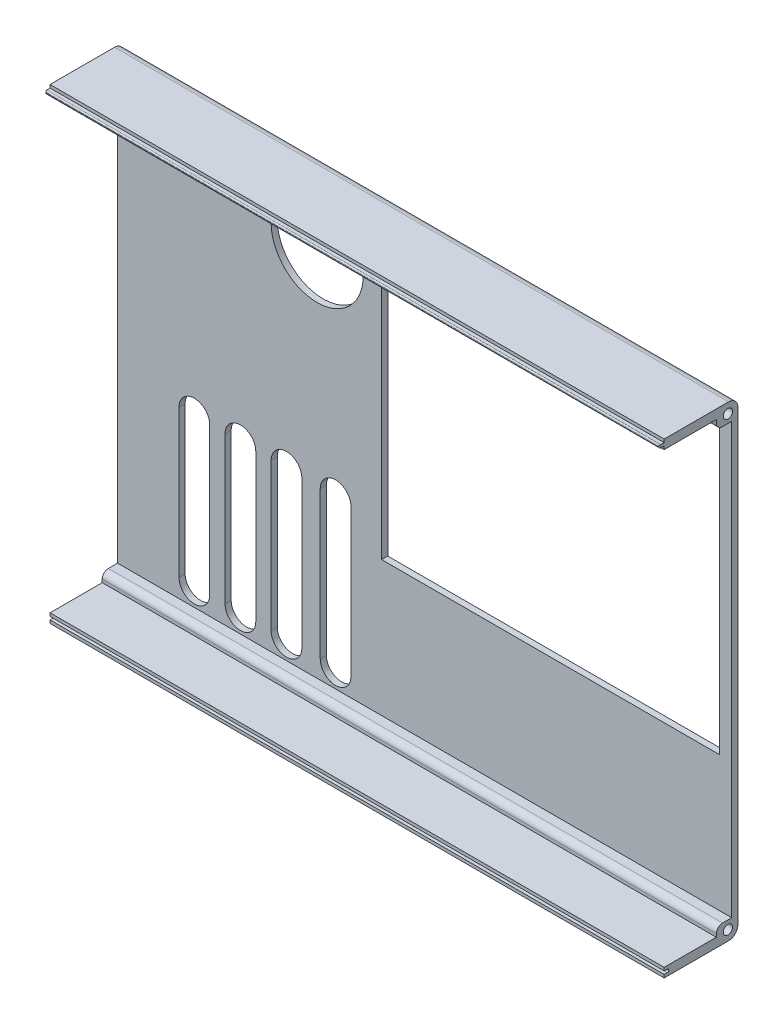
SolidWorks part; units mm, degrees
ref_plane "Front Plane" through (0, 0, 0) normal (0, 0, 1) x (1, 0, 0)
ref_plane "Top Plane" through (0, 0, 0) normal (0, 1, 0) x (1, 0, 0)
ref_plane "Right Plane" through (0, 0, 0) normal (1, 0, 0) x (0, 0, -1)
sketch "Sketch1" plane through (0, 0, 0) normal (0, 0, 1) x (1, 0, 0)
  line L1 (105, -90.3987) -> (-95, -90.3987)
  line L2 (105, -90.3987) -> (105, 61.6013)
  line L3 (105, 61.6013) -> (-95, 61.6013)
  line L4 (-95, -90.3987) -> (-95, 61.6013)
  line L5 (105, -90.3987) -> (-95, 61.6013) construction
  line L6 (105, 61.6013) -> (-95, -90.3987) construction
  point P0 (5, -14.3987)
  dimension "D1" = 200
  dimension "D2" = 152
extrude "body" add sketch "Sketch1" along normal blind 2
sketch "Sketch3" plane through (0, 0, 0) normal (0, 0, -1) x (-1, 0, 0)
  line L0 (95, -54.3987) -> (-105, -54.3987) construction
  line L1 (95, 61.6013) -> (95, -90.3987) construction
  line L2 (-105, -90.3987) -> (-105, 61.6013) construction
  line L3 (55, -78.3987) -> (55, -30.3987) construction
  line L4 (50, -78.3987) -> (50, -30.3987)
  line L5 (60, -78.3987) -> (60, -30.3987)
  line L6 (95, -30.3987) -> (-105, -30.3987) construction
  line L7 (70, -78.3987) -> (70, -30.3987) construction
  line L8 (95, -78.3987) -> (-105, -78.3987) construction
  line L9 (65, -78.3987) -> (65, -30.3987)
  line L10 (75, -78.3987) -> (75, -30.3987)
  line L11 (40, -78.3987) -> (40, -30.3987) construction
  line L12 (35, -78.3987) -> (35, -30.3987)
  line L13 (45, -78.3987) -> (45, -30.3987)
  line L14 (24, -78.3987) -> (24, -30.3987) construction
  line L15 (19, -78.3987) -> (19, -30.3987)
  line L16 (29, -78.3987) -> (29, -30.3987)
  line L17 (95, -90.3987) -> (95, 61.6013) construction
  line L18 (-105, 61.6013) -> (95, 61.6013) construction
  line L19 (95, -90.3987) -> (-105, -90.3987) construction
  line L20 (-105, -90.3987) -> (-105, 61.6013) construction
  circle A0 centre (30, 36.6013) radius 15
  arc A1 (50, -78.3987) -> (60, -78.3987) centre (55, -78.3987) ccw
  arc A2 (60, -30.3987) -> (50, -30.3987) centre (55, -30.3987) ccw
  arc A3 (65, -78.3987) -> (75, -78.3987) centre (70, -78.3987) ccw
  arc A4 (75, -30.3987) -> (65, -30.3987) centre (70, -30.3987) ccw
  arc A5 (35, -78.3987) -> (45, -78.3987) centre (40, -78.3987) ccw
  arc A6 (45, -30.3987) -> (35, -30.3987) centre (40, -30.3987) ccw
  arc A7 (19, -78.3987) -> (29, -78.3987) centre (24, -78.3987) ccw
  arc A8 (29, -30.3987) -> (19, -30.3987) centre (24, -30.3987) ccw
  point P10 (55, -54.3987)
  point P21 (70, -54.3987)
  point P27 (40, -54.3987)
  point P34 (24, -54.3987)
  dimension "D1" = 30
  dimension "D2" = 25
  dimension "D3" = 65
  dimension "D4" = 20
  dimension "D5" = 12
  dimension "D6" = 24
  dimension "D8" = 10
  dimension "D9" = 10
  dimension "D10" = 10
  dimension "D11" = 10
  dimension "D12" = 5
  dimension "D13" = 56
  dimension "D14" = 5
extrude "fan_exhaust_grill" cut sketch "Sketch3" against normal through all
sketch "Sketch12" plane through (0, 0, 2) normal (0, 0, 1) x (1, 0, 0)
  line L0 (-95, -90.3987) -> (-95, 61.6013) construction
  line L1 (105, -90.3987) -> (-95, -90.3987)
  line L2 (105, -90.3987) -> (105, -84.3987)
  line L3 (105, -84.3987) -> (-95, -84.3987)
  line L4 (-95, -90.3987) -> (-95, -84.3987)
  line L6 (105, 61.6013) -> (-95, 61.6013)
  line L7 (105, 61.6013) -> (105, 55.6013)
  line L8 (105, 55.6013) -> (-95, 55.6013)
  line L9 (-95, 61.6013) -> (-95, 55.6013)
  dimension "D1" = 6
  dimension "D2" = 6
extrude "side_walls" add sketch "Sketch12" along normal blind 22
sketch "Sketch14" plane through (105, 0, 0) normal (1, 0, 0) x (0, 0, -1)
  line L0 (-24, -90.3987) -> (0, -90.3987) construction
  line L1 (0, -90.3987) -> (0, 61.6013) construction
  line L2 (-24, 61.6013) -> (0, 61.6013) construction
  circle A0 centre (-3.25, -87.1487) radius 1.5
  circle A1 centre (-3.25, 58.3513) radius 1.5
  point P8 (-3.0136, -90.3987)
  dimension "D1" = 3
  dimension "D2" = 3
  dimension "D3" = 3.25
  dimension "D4" = 3.25
  dimension "D5" = 3.25
  dimension "D6" = 3.25
  dimension "D7" = 145.5
extrude "mount_holes_l" cut sketch "Sketch14" against normal blind 10 and the other way through all
sketch "Sketch16" plane through (-95, 0, 0) normal (-1, 0, 0) x (0, 0, 1)
  line L0 (0, -90.3987) -> (0, 61.6013) construction
  line L2 (24, 61.6013) -> (0, 61.6013) construction
  line L3 (24, -90.3987) -> (0, -90.3987) construction
  circle A0 centre (3.25, -87.1487) radius 1.5
  circle A1 centre (3.25, 58.3513) radius 1.5
  point P8 (1.638, 61.6013)
  dimension "D1" = 3
  dimension "D4" = 3
  dimension "D2" = 3.25
  dimension "D3" = 3.25
  dimension "D5" = 3.25
  dimension "D6" = 3.25
extrude "mount_holes_r" cut sketch "Sketch16" against normal blind 10
sketch "Sketch18" plane through (105, 0, 0) normal (1, 0, 0) x (0, 0, -1)
  line L1 (-24, -84.3987) -> (-7, -84.3987)
  line L2 (-24, -84.3987) -> (-24, -87.3987)
  line L3 (-24, -87.3987) -> (-7, -87.3987)
  line L4 (-7, -84.3987) -> (-7, -87.3987)
  line L5 (-24, 55.6013) -> (-7, 55.6013)
  line L6 (-24, 55.6013) -> (-24, 58.6013)
  line L7 (-24, 58.6013) -> (-7, 58.6013)
  line L8 (-7, 55.6013) -> (-7, 58.6013)
  dimension "D1" = 3
  dimension "D2" = 17
  dimension "D3" = 3
  dimension "D4" = 17
extrude "wall_reduce" cut sketch "Sketch18" against normal through all
sketch "Sketch19" plane through (0, 0, 24) normal (0, 0, 1) x (1, 0, 0)
  line L0 (-95, -90.3987) -> (-95, 61.6013) construction
  line L1 (-95, -89.3987) -> (105, -89.3987)
  line L2 (-95, -89.3987) -> (-95, -88.3987)
  line L3 (-95, -88.3987) -> (105, -88.3987)
  line L4 (105, -89.3987) -> (105, -88.3987)
  line L5 (105, -90.3987) -> (105, 61.6013) construction
  line L6 (-95, -90.3987) -> (105, -90.3987) construction
  dimension "D1" = 1
  dimension "D2" = 1
extrude "groove" cut sketch "Sketch19" against normal blind 1.5
sketch "Sketch20" plane through (0, 0, 24) normal (0, 0, 1) x (1, 0, 0)
  line L0 (-95, -90.3987) -> (-95, 61.6013) construction
  line L1 (-95, 59.6013) -> (105, 59.6013)
  line L2 (-95, 59.6013) -> (-95, 60.6013)
  line L3 (-95, 60.6013) -> (105, 60.6013)
  line L4 (105, 59.6013) -> (105, 60.6013)
  line L5 (105, -90.3987) -> (105, 61.6013) construction
  line L6 (105, 61.6013) -> (-95, 61.6013) construction
  dimension "D1" = 1
  dimension "D2" = 1
extrude "notch" add sketch "Sketch20" along normal blind 1.5
sketch "Sketch21" plane through (0, 0, 2) normal (0, 0, 1) x (1, 0, 0)
  line L0 (105, -90.3987) -> (105, 61.6013) construction
  line L1 (101, -40.3987) -> (-9, -40.3987)
  line L2 (101, -40.3987) -> (101, 54.6013)
  line L3 (101, 54.6013) -> (-9, 54.6013)
  line L4 (-9, -40.3987) -> (-9, 54.6013)
  line L5 (105, 61.6013) -> (-95, 61.6013) construction
  dimension "D1" = 110
  dimension "D2" = 95
  dimension "D3" = 4
  dimension "D4" = 7
extrude "batt_cut" cut sketch "Sketch21" against normal through all
fillet "Fillet1" radius 3 2 edges at (5, -90.3987, 0) (5, 61.6013, 0)
fillet "Fillet2" radius 2 2 edges at (5, -84.3987, 7) (5, 55.6013, 7)
fillet "Fillet3" radius 0.4 6 edges at (5, 60.6013, 25.5) (105, 60.1013, 25.5) (5, 59.6013, 25.5) (-95, 60.1013, 25.5) (5, -89.3987, 22.5) (5, -88.3987, 22.5)
